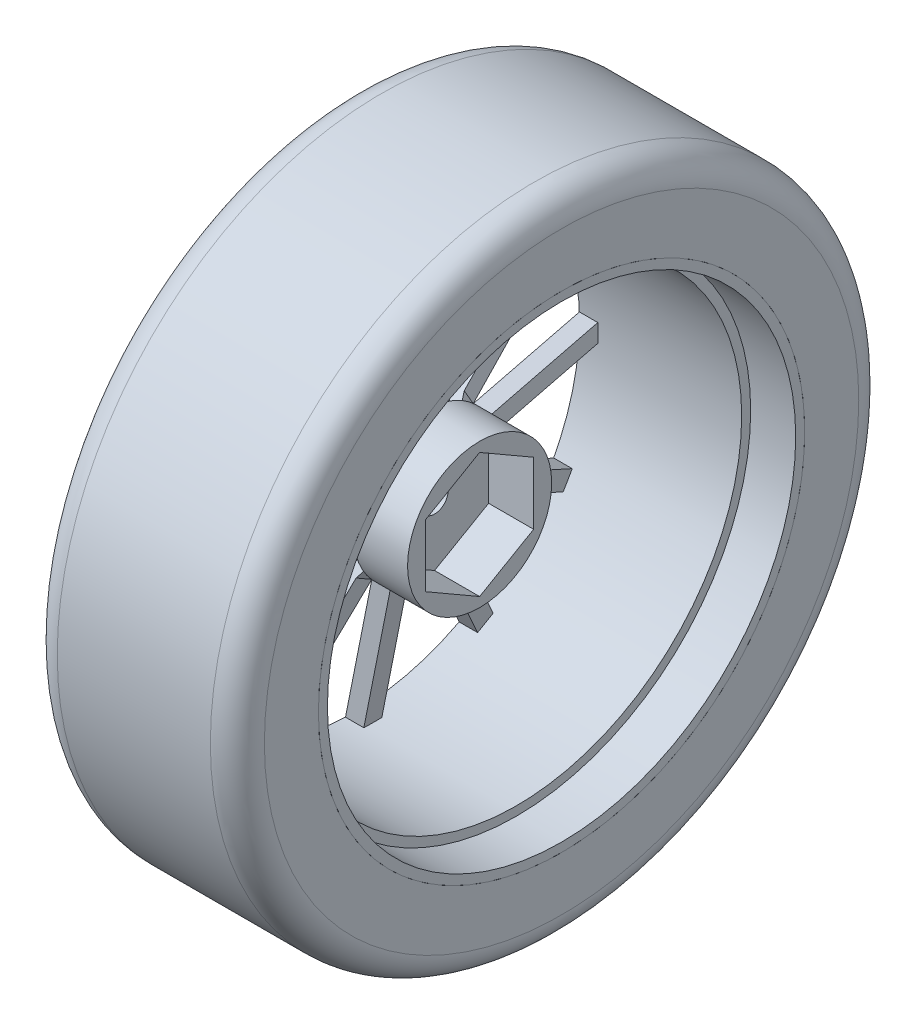
SolidWorks part; units mm, degrees
ref_plane "Front Plane" through (0, 0, 0) normal (0, 0, 1) x (1, 0, 0)
ref_plane "Top Plane" through (0, 0, 0) normal (0, 1, 0) x (1, 0, 0)
ref_plane "Right Plane" through (0, 0, 0) normal (1, 0, 0) x (0, 0, -1)
sketch "Sketch1" plane through (0, 0, 0) normal (1, 0, 0) x (0, 0, -1)
  line L1 (0, 6.9282) -> (-6, 3.4641)
  line L2 (-6, 3.4641) -> (-6, -3.4641)
  line L3 (-6, -3.4641) -> (0, -6.9282)
  line L4 (0, -6.9282) -> (6, -3.4641)
  line L5 (6, -3.4641) -> (6, 3.4641)
  line L6 (6, 3.4641) -> (0, 6.9282)
  circle A0 centre (0, 0) radius 6 construction
  circle A1 centre (0, 0) radius 8
  dimension "D1" = 12
  dimension "D2" = 16
extrude "Boss-Extrude1" add sketch "Sketch1" along normal blind 5
sketch "Sketch2" plane through (0, 0, 0) normal (-1, 0, 0) x (0, 0, 1)
  circle A1 centre (0, 0) radius 8
  circle A2 centre (0, 0) radius 8
  dimension "D1" = 0
extrude "Boss-Extrude2" add sketch "Sketch2" along normal blind 1 separate body
sketch "Sketch3" plane through (-1, 0, 0) normal (-1, 0, 0) x (0, 0, 1)
  circle A0 centre (0, 0) radius 1.5
  dimension "D1" = 3
extrude "Cut-Extrude1" cut sketch "Sketch3" against normal blind 3
sketch "Sketch4" plane through (0, 0, 0) normal (0, 1, 0) x (1, 0, 0)
  line L0 (0, 0) -> (-1, 0)
  line L1 (-1, 8) -> (-1, -8) construction
  line L2 (-1, 0) -> (-5.4812, 7.805)
  line L3 (-5.4812, 7.805) -> (-8.8984, 25)
  line L4 (0.1617, 1.9935) -> (0.1617, 1.9935)
  line L5 (-1, 4.0168) -> (-3.5835, 8.5165)
  line L6 (-3.5835, 8.5165) -> (-6.8592, 25)
  line L7 (-3.5835, 8.5165) -> (-5.9119, 20.2331) construction
  line L8 (-1, 0) -> (-1, 4.0168)
  line L9 (0.1617, 1.9935) -> (-3.5835, 8.5165) construction
  line L11 (-5.4812, 7.805) -> (-7.8736, 19.8432) construction
  line L13 (-6.8592, 25) -> (-8.8984, 25)
  dimension "D3" = 9
  dimension "D4" = 2
extrude "Boss-Extrude3" add sketch "Sketch4" along normal mid plane 2 separate body contours L6 L3 L2 L8 L5 region at (-5.2172, 0, -13.1872)
sketch "Sketch5" plane through (0, 0, 0) normal (1, 0, 0) x (0, 0, -1)
  circle A0 centre (0, 0) radius 1.5
extrude "Cut-Extrude2" cut sketch "Sketch5" against normal blind 50
pattern_circular "CirPattern3" count 12 over 360 about axis through (-1, 0, 0) along (-1, 0, 0) of bodies 105
ref_plane "Plane3" through (-8.9, 0, 0) normal (1, 0, 0) x (0, 0, -1)
sketch "Sketch12" plane through (-8.9, 0, 0) normal (1, 0, 0) x (0, 0, -1)
  circle A0 centre (0, 0) radius 27
  circle A1 centre (0, 0) radius 25
  dimension "D1" = 54
  dimension "D2" = 2
extrude "Boss-Extrude5" add sketch "Sketch12" along normal blind 2
sketch "Sketch14" plane through (-8.9, 0, 0) normal (-1, 0, 0) x (0, 0, 1)
  circle A0 centre (0, 0) radius 36
  circle A1 centre (0, 0) radius 27 construction
  circle A2 centre (0, 0) radius 27
  circle A3 centre (0, 0) radius 25
  circle M2 centre (0, 0) radius 27
  circle M3 centre (0, 0) radius 25
  dimension "D1" = 72
extrude "Boss-Extrude7" add sketch "Sketch14" against normal blind 3 contours M2 M3 region at (-8.9, 0, -26.2363)
sketch "Sketch15" plane through (-5.9, 0, 0) normal (1, 0, 0) x (0, 0, -1)
  circle A0 centre (0, 0) radius 26
  circle A1 centre (0, 0) radius 25 construction
  circle A3 centre (0, 0) radius 25
  dimension "D2" = 52
extrude "Boss-Extrude8" add sketch "Sketch15" along normal blind 15
sketch "Sketch16" plane through (9.1, 0, 0) normal (1, 0, 0) x (0, 0, -1)
  circle A0 centre (0, 0) radius 27
  circle A1 centre (0, 0) radius 26 construction
  circle A2 centre (0, 0) radius 26
  dimension "D1" = 54
extrude "Boss-Extrude9" add sketch "Sketch16" along normal blind 5 separate body
sketch "Sketch17" plane through (-8.9, 0, 0) normal (-1, 0, 0) x (0, 0, 1)
  circle A0 centre (0, 0) radius 36
  circle A1 centre (0, 0) radius 27 construction
  circle A2 centre (0, 0) radius 27
  dimension "D1" = 72
extrude "Boss-Extrude10" add sketch "Sketch17" against normal blind 23 separate body
fillet "Fillet3" radius 3 2 edges at (14.1, 0, 36) (-8.9, 0, 36)
ref_plane "Plane4" through (0, 36, 0) normal (0, 1, 0) x (1, 0, 0)
